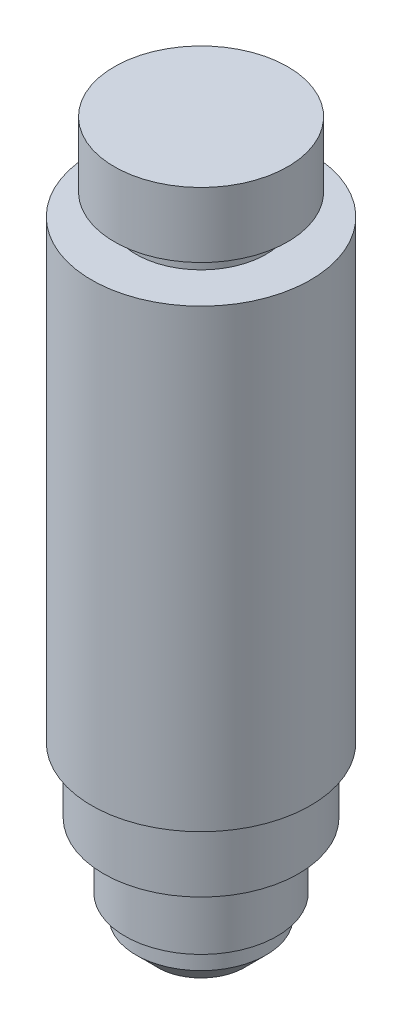
SolidWorks part; units mm, degrees
ref_plane "Front Plane" through (0, 0, 0) normal (0, 0, 1) x (1, 0, 0)
ref_plane "Top Plane" through (0, 0, 0) normal (0, 1, 0) x (1, 0, 0)
ref_plane "Right Plane" through (0, 0, 0) normal (1, 0, 0) x (0, 0, -1)
sketch "Sketch1" plane through (0, 0, 0) normal (0, 0, 1) x (1, 0, 0)
  line L0 (12.827, 73.66) -> (12.827, 20.32)
  line L1 (12.827, 20.32) -> (11.43, 20.32)
  line L2 (11.43, 20.32) -> (11.43, 12.7)
  line L3 (11.43, 12.7) -> (7.62, 12.7)
  line L4 (7.62, 12.7) -> (7.62, 11.43)
  line L5 (7.62, 11.43) -> (8.89, 11.43)
  line L6 (8.89, 11.43) -> (8.89, 5.08)
  line L7 (8.89, 5.08) -> (7.62, 5.08)
  line L8 (7.62, 5.08) -> (7.62, 2.54)
  line L9 (7.62, 2.54) -> (5.08, 2.54)
  line L10 (5.08, 2.54) -> (5.08, 0)
  line L11 (5.08, 0) -> (0, 0)
  line L12 (0, 0) -> (0, 83.82)
  line L13 (0, 83.82) -> (10.16, 83.82)
  line L14 (10.16, 83.82) -> (10.16, 76.2)
  line L15 (10.16, 76.2) -> (7.62, 76.2)
  line L16 (7.62, 76.2) -> (7.62, 73.66)
  line L17 (7.62, 73.66) -> (12.827, 73.66)
  dimension "D1" = 60.96
  dimension "D2" = 12.827
  dimension "D3" = 10.16
  dimension "D4" = 7.62
  dimension "D5" = 2.54
  dimension "D6" = 7.62
  dimension "D7" = 11.43
  dimension "D8" = 7.62
  dimension "D9" = 5.08
  dimension "D10" = 2.54
  dimension "D11" = 7.62
  dimension "D12" = 8.89
  dimension "D13" = 2.54
  dimension "D14" = 1.27
  dimension "D15" = 6.35
revolve "Revolve1" add sketch "Sketch1" angle 360 about L12
chamfer "Chamfer1" distance 2.54 angle 45 1 edges at (0, 2.54, -5.08)
